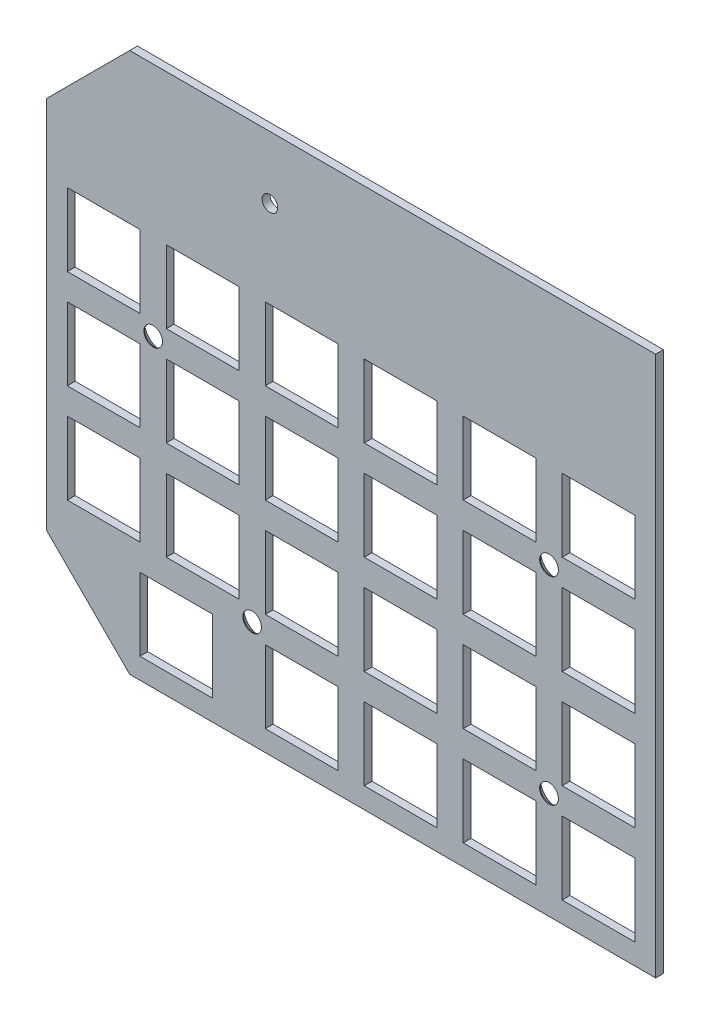
SolidWorks part; units mm, degrees
material "Alliage 1060"
ref_plane "Plan de face" through (0, 0, 0) normal (0, 0, 1) x (1, 0, 0)
ref_plane "Plan de dessus" through (0, 0, 0) normal (0, 1, 0) x (1, 0, 0)
ref_plane "Plan de droite" through (0, 0, 0) normal (1, 0, 0) x (0, 0, -1)
sketch "Esquisse1" plane through (0, 0, 0) normal (0, 0, 1) x (1, 0, 0)
  line L0 (0, -85) -> (16, -101)
  line L4 (117.25, 3) -> (117.25, -101)
  line L5 (16, 3) -> (0, -13)
  line L7 (117.25, 3) -> (16, 3)
  line L8 (0, -13) -> (0, -85)
  line L9 (16, -101) -> (117.25, -101)
  dimension "D1" = 104
  dimension "D2" = 117.25
  dimension "D3" = 16
  dimension "D4" = 16
  dimension "D5" = 16
  dimension "D6" = 16
extrude "Boss.-Extru.1" add sketch "Esquisse1" along normal blind 1.5
sketch "Esquisse3" plane through (0, 0, 0) normal (0, 0, -1) x (-1, 0, 0)
  line L0 (-94.2, -25.85) -> (-94.2, -39.85)
  line L1 (-113.25, -25.85) -> (-99.25, -25.85)
  line L2 (-113.25, -25.85) -> (-113.25, -39.85)
  line L3 (-113.25, -39.85) -> (-99.25, -39.85)
  line L4 (-99.25, -25.85) -> (-99.25, -39.85)
  line L5 (-106.25, -39.85) -> (-106.25, -25.85) construction
  line L6 (-113.25, -32.85) -> (-99.25, -32.85) construction
  line L7 (-94.2, -25.85) -> (-80.2, -25.85)
  line L8 (-80.2, -25.85) -> (-80.2, -39.85)
  line L9 (-94.2, -39.85) -> (-80.2, -39.85)
  line L10 (-75.15, -25.85) -> (-75.15, -39.85)
  line L11 (-75.15, -25.85) -> (-61.15, -25.85)
  line L12 (-61.15, -25.85) -> (-61.15, -39.85)
  line L13 (-75.15, -39.85) -> (-61.15, -39.85)
  line L14 (-56.1, -25.85) -> (-56.1, -39.85)
  line L15 (-56.1, -25.85) -> (-42.1, -25.85)
  line L16 (-42.1, -25.85) -> (-42.1, -39.85)
  line L17 (-56.1, -39.85) -> (-42.1, -39.85)
  line L18 (-37.05, -25.85) -> (-37.05, -39.85)
  line L19 (-37.05, -25.85) -> (-23.05, -25.85)
  line L20 (-23.05, -25.85) -> (-23.05, -39.85)
  line L21 (-37.05, -39.85) -> (-23.05, -39.85)
  line L22 (-18, -25.85) -> (-18, -39.85)
  line L23 (-18, -25.85) -> (-4, -25.85)
  line L24 (-4, -25.85) -> (-4, -39.85)
  line L25 (-18, -39.85) -> (-4, -39.85)
  line L26 (-94.2, -44.9) -> (-94.2, -58.9)
  line L27 (-94.2, -44.9) -> (-80.2, -44.9)
  line L28 (-80.2, -44.9) -> (-80.2, -58.9)
  line L29 (-94.2, -58.9) -> (-80.2, -58.9)
  line L30 (-75.15, -44.9) -> (-75.15, -58.9)
  line L31 (-75.15, -44.9) -> (-61.15, -44.9)
  line L32 (-61.15, -44.9) -> (-61.15, -58.9)
  line L33 (-75.15, -58.9) -> (-61.15, -58.9)
  line L34 (-56.1, -44.9) -> (-56.1, -58.9)
  line L35 (-56.1, -44.9) -> (-42.1, -44.9)
  line L36 (-42.1, -44.9) -> (-42.1, -58.9)
  line L37 (-56.1, -58.9) -> (-42.1, -58.9)
  line L38 (-37.05, -44.9) -> (-37.05, -58.9)
  line L39 (-37.05, -44.9) -> (-23.05, -44.9)
  line L40 (-23.05, -44.9) -> (-23.05, -58.9)
  line L41 (-37.05, -58.9) -> (-23.05, -58.9)
  line L42 (-18, -44.9) -> (-18, -58.9)
  line L43 (-18, -44.9) -> (-4, -44.9)
  line L44 (-4, -44.9) -> (-4, -58.9)
  line L45 (-18, -58.9) -> (-4, -58.9)
  line L46 (-94.2, -63.95) -> (-94.2, -77.95)
  line L47 (-94.2, -63.95) -> (-80.2, -63.95)
  line L48 (-80.2, -63.95) -> (-80.2, -77.95)
  line L49 (-94.2, -77.95) -> (-80.2, -77.95)
  line L50 (-75.15, -63.95) -> (-75.15, -77.95)
  line L51 (-75.15, -63.95) -> (-61.15, -63.95)
  line L52 (-61.15, -63.95) -> (-61.15, -77.95)
  line L53 (-75.15, -77.95) -> (-61.15, -77.95)
  line L54 (-56.1, -63.95) -> (-56.1, -77.95)
  line L55 (-56.1, -63.95) -> (-42.1, -63.95)
  line L56 (-42.1, -63.95) -> (-42.1, -77.95)
  line L57 (-56.1, -77.95) -> (-42.1, -77.95)
  line L58 (-37.05, -63.95) -> (-37.05, -77.95)
  line L59 (-37.05, -63.95) -> (-23.05, -63.95)
  line L60 (-23.05, -63.95) -> (-23.05, -77.95)
  line L61 (-37.05, -77.95) -> (-23.05, -77.95)
  line L62 (-18, -63.95) -> (-18, -77.95)
  line L63 (-18, -63.95) -> (-4, -63.95)
  line L64 (-4, -63.95) -> (-4, -77.95)
  line L65 (-18, -77.95) -> (-4, -77.95)
  line L66 (-94.2, -83) -> (-94.2, -97)
  line L67 (-94.2, -83) -> (-80.2, -83)
  line L68 (-80.2, -83) -> (-80.2, -97)
  line L69 (-94.2, -97) -> (-80.2, -97)
  line L70 (-75.15, -83) -> (-75.15, -97)
  line L71 (-75.15, -83) -> (-61.15, -83)
  line L72 (-61.15, -83) -> (-61.15, -97)
  line L73 (-75.15, -97) -> (-61.15, -97)
  line L74 (-56.1, -83) -> (-56.1, -97)
  line L75 (-56.1, -83) -> (-42.1, -83)
  line L76 (-42.1, -83) -> (-42.1, -97)
  line L77 (-56.1, -97) -> (-42.1, -97)
  line L86 (-113.25, -44.9) -> (-113.25, -58.9)
  line L87 (-113.25, -44.9) -> (-99.25, -44.9)
  line L88 (-99.25, -44.9) -> (-99.25, -58.9)
  line L89 (-113.25, -58.9) -> (-99.25, -58.9)
  line L90 (-113.25, -63.95) -> (-113.25, -77.95)
  line L91 (-113.25, -63.95) -> (-99.25, -63.95)
  line L92 (-99.25, -63.95) -> (-99.25, -77.95)
  line L93 (-113.25, -77.95) -> (-99.25, -77.95)
  line L94 (-113.25, -83) -> (-113.25, -97)
  line L95 (-113.25, -83) -> (-99.25, -83)
  line L96 (-99.25, -83) -> (-99.25, -97)
  line L97 (-113.25, -97) -> (-99.25, -97)
  line L98 (-4, -83) -> (-4, -97) [skipped]
  line L99 (-18, -97) -> (-4, -97) [skipped]
  line L100 (-18, -83) -> (-18, -97) [skipped]
  line L101 (-18, -83) -> (-4, -83) [skipped]
  line L103 (-117.25, -101) -> (-117.25, 3) construction
  line L104 (-16, -101) -> (-117.25, -101) construction
  line L107 (-37.05, -83) -> (-23.05, -83) [skipped]
  line L108 (-23.05, -83) -> (-23.05, -97) [skipped]
  line L109 (-37.05, -83) -> (-37.05, -97) [skipped]
  line L110 (-37.05, -97) -> (-23.05, -97) [skipped]
  line L111 (0, -13) -> (0, -85) construction
  line L112 (-31.97, -83) -> (-17.97, -83)
  line L113 (-31.97, -83) -> (-31.97, -97)
  line L114 (-31.97, -97) -> (-17.97, -97)
  line L115 (-17.97, -83) -> (-17.97, -97)
  line L116 (-24.97, -97) -> (-24.97, -83) construction
  line L117 (-31.97, -90) -> (-17.97, -90) construction
  line L122 (-117.25, 3) -> (-16, 3) construction
  circle A5 centre (-43, -9) radius 1.5
  point P0 (-106.25, -32.85)
  point P84 (-24.97, -90)
  dimension "D7" = 43
  dimension "D8" = 12
  dimension "D1" = 14
  dimension "D2" = 14
  dimension "D5" = 4
  dimension "D6" = 4
  dimension "D9" = 5.05
  dimension "D10" = 14
  dimension "D11" = 14
  dimension "D12" = 10.13
  dimension "D13" = 5.05
  dimension "D3" = 6
  dimension "D4" = 4
extrude "Enlèv. mat.-Extru.2" cut sketch "Esquisse3" against normal blind 10
sketch "Esquisse4" plane through (0, 0, 0) normal (0, 0, -1) x (-1, 0, 0)
  line L0 (-99.25, -39.85) -> (-94.2, -44.9) construction
  line L1 (-23.05, -39.85) -> (-18, -44.9) construction
  line L2 (-37.05, -77.95) -> (-42.1, -83) construction
  line L3 (-94.2, -77.95) -> (-99.25, -83) construction
  point P16 (-96.725, -42.375)
  point P17 (-96.725, -80.475)
  point P18 (-39.575, -80.475)
hole_wizard "Fraisage pour vis à tête fraisée M31" positions "Esquisse5" profile "Esquisse6" countersink size "M3" standard "Ansi Metric" end condition through all
sketch "Esquisse5" plane through (0, 0, 0) normal (0, 0, -1) x (-1, 0, 0)
  line L0 (-23.05, -39.85) -> (-18, -44.9) construction
  line L1 (-37.05, -77.95) -> (-42.1, -83) construction
  point P0 (-96.725, -42.375)
  point P3 (-96.725, -80.475)
  point P6 (-20.525, -42.375)
  point P10 (-39.575, -80.475)
sketch "Esquisse6" plane through (96.725, -42.375, 0) normal (1, 0, 0) x (0, 1, 0)
  line L0 (0, 0) -> (0, 1.5)
  line L1 (0, 1.5) -> (1.8, 1.5)
  line L2 (1.8, 1.5) -> (1.8, 1.35)
  line L3 (1.8, 1.35) -> (3.15, 0)
  line L5 (3.15, 0) -> (0, 0)
  line L6 (-1.8, 1.35) -> (-3.15, 0) construction
  line L11 (0, -6.35) -> (0, 107.95) construction
  dimension "Diamètre du perçage jusqu'au prochain" = 3.6
  dimension "Profondeur du perçage jusqu'au prochain" = 1.5
  dimension "Diamètre du fraisage entrant" = 6.3
  dimension "Angle du fraisage entrant" = 90
